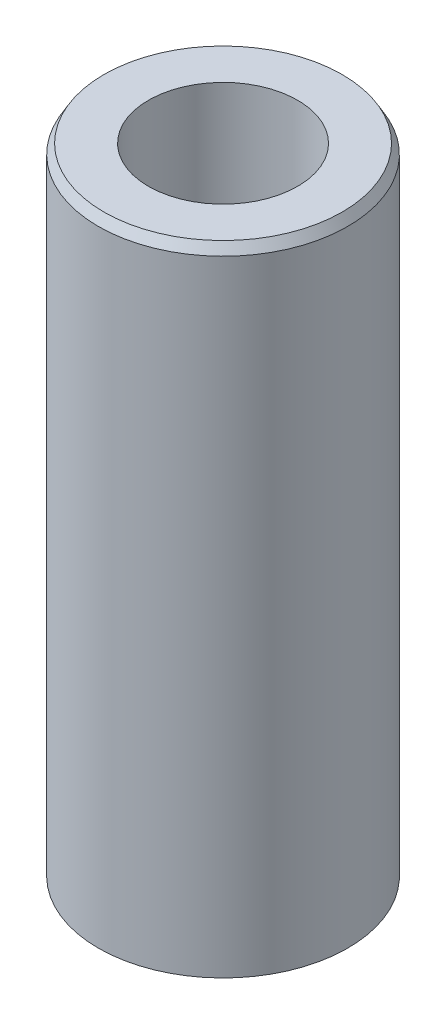
SolidWorks part; units mm, degrees
ref_plane "Front Plane" through (0, 0, 0) normal (0, 0, 1) x (1, 0, 0)
ref_plane "Top Plane" through (0, 0, 0) normal (0, 1, 0) x (1, 0, 0)
ref_plane "Right Plane" through (0, 0, 0) normal (1, 0, 0) x (0, 0, -1)
sketch "Sketch1" plane through (0, 0, 0) normal (0, 1, 0) x (1, 0, 0)
  circle A0 centre (0, 0) radius 7.5
  dimension "SHAFT_OD" = 15
extrude "Boss-Extrude1" add sketch "Sketch1" along normal blind 38.5029
sketch "Sketch2" plane through (0, 0, 0) normal (0, 1, 0) x (1, 0, 0)
  circle A0 centre (0, 0) radius 4.4868
  dimension "BORE_D" = 8.9736
extrude "Cut-Extrude1" cut sketch "Sketch2" along normal through all
chamfer "Chamfer1" distance 0.5808 angle 30 2 edges at (0, 38.5029, 7.5) (0, 0, 7.5) first distance on face at (0, 38.5029, 7.5) first distance on face at (0, 0, 4.4868)
